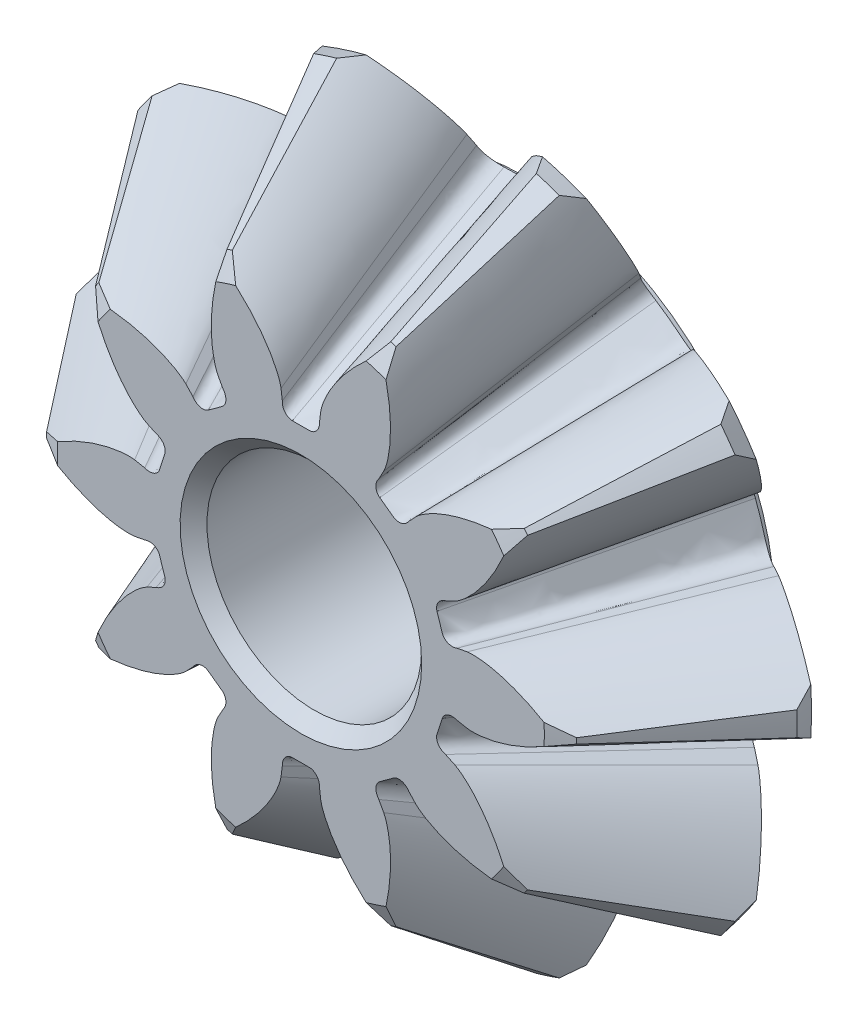
SolidWorks part; units mm, degrees
ref_plane "Płaszczyzna przednia" through (0, 0, 0) normal (0, 0, 1) x (1, 0, 0)
ref_plane "Płaszczyzna górna" through (0, 0, 0) normal (0, 1, 0) x (1, 0, 0)
ref_plane "Płaszczyzna prawa" through (0, 0, 0) normal (1, 0, 0) x (0, 0, -1)
ref_axis "Oś1" through (0, 0, -111.4398) along (0, 0, 1)
sketch "Bevel-BaseSketch" plane through (0, 0, 0) normal (1, 0, 0) x (0, 0, -1)
  line L0 (38.5248, 0) -> (38.5248, 18.461) construction
  line L1 (38.5248, 18.461) -> (33.4298, 26.613)
  line L2 (32.1052, 26.8539) -> (22.7963, 19.7412)
  line L3 (22.0017, 18.1341) -> (22.0017, 0)
  line L4 (22.0017, 0) -> (38.5248, 0)
  line L5 (38.5248, 0) -> (8.9872, 0) construction
  line L6 (38.8355, 18.461) -> (38.5248, 18.461)
  line L8 (88.99, 0) -> (-88.99, 0) construction
  line L9 (43, 0) -> (38.5248, 0)
  line L10 (22.7963, 19.7412) -> (22.0017, 18.1341)
  line L11 (33.4298, 26.613) -> (32.1052, 26.8539)
  arc A0 (43, 0) -> (38.8355, 18.461) centre (0, 0) ccw
  point P3 (32.8998, 27.461)
  point P4 (22.0017, 19.1341)
  dimension "D1" = 43
  dimension "Hub Mounting" = 38.5248
  dimension "Back Cone" = 10.6133
  dimension "Face Width" = 13.7151
  dimension "Body Width" = 16.523
  dimension "Face Angle" = 37.383
  dimension "D2" = 27.461
revolve "Obrót1" add sketch "Bevel-BaseSketch" angle 360 about L5
ref_axis "Oś2" through (-30.2071, 0, 0) along (1, 0, 0)
ref_plane "PlaneAtAngle" through (0, 0, 0) normal (0, 0.53, -0.848) x (1, 0, 0)
ref_plane "PlaneAtOffset" through (0, 22.5002, -36.0003) normal (0, 0.53, -0.848) x (1, 0, 0)
sketch "Tooth-Sketch; Clearance: 0,0000mm" plane through (0, 22.5002, -36.0003) normal (0, 0.53, -0.848) x (1, 0, 0)
  line L0 (0, 0) -> (0, -24.9331) construction
  line L1 (-2.3603, 2.8443) -> (-2.4837, 1.7242)
  line L2 (2.3603, 2.8443) -> (2.4837, 1.7242)
  line L3 (0, -8.4605) -> (-12.2635, -7.7622)
  line L4 (0, -8.4605) -> (12.2635, -7.7622)
  line L5 (1.0989, 4.2523) -> (-1.0989, 4.2523)
  arc A0 (-2.3603, 2.8443) -> (-1.0989, 4.2523) centre (-1.0989, 2.9833) cw
  arc A1 (2.3603, 2.8443) -> (1.0989, 4.2523) centre (1.0989, 2.9833) ccw
  spline S0 degree 3 poles (-12.2635, -7.7622) (-9.6322, -6.4655) (-6.5832, -4.5569) (-4.0813, -1.5452) (-3.3688, -0.4741) (-2.9045, 0.4127) (-2.6249, 1.1215) (-2.5104, 1.5356) (-2.4837, 1.7242) knots 0 0 0 0 0.633198 0.745276 0.836976 0.908298 0.959242 1 1 1 1
  spline S1 degree 3 poles (12.2635, -7.7622) (9.6322, -6.4655) (6.5832, -4.5569) (4.0813, -1.5452) (3.3688, -0.4741) (2.9045, 0.4127) (2.6249, 1.1215) (2.5104, 1.5356) (2.4837, 1.7242) knots 0 0 0 0 0.633198 0.745276 0.836976 0.908298 0.959242 1 1 1 1
  point P28 (0, 4.2523)
sketch "Apex" plane through (0, 0, 0) normal (1, 0, 0) x (0, 0, -1)
  point P0 (0, 0)
loft "Tooth-Cut, 20 Degree P.A." cut profiles "Tooth-Sketch; Clearance: 0,0000mm", "Apex"
pattern_circular "Szyk kołowy2" count 10 over 360 about axis through (0, 0, -111.4398) along (0, 0, 1) of "Tooth-Cut, 20 Degree P.A."
sketch "Szkic1" plane through (0, 0, -22.0017) normal (0, 0, 1) x (1, 0, 0)
  circle A0 centre (0, 0) radius 8
  dimension "D1" = 16
extrude "Wytnij-wyciągnięcie1" cut sketch "Szkic1" against normal up to next
chamfer "Sfazowanie1" distance 1 angle 45 2 edges at (8, 0, -22.0017) (8, 0, -42.2493) first distance on face at (8, 0, -22.0017) first distance on face at (8, 0, -42.2493)
